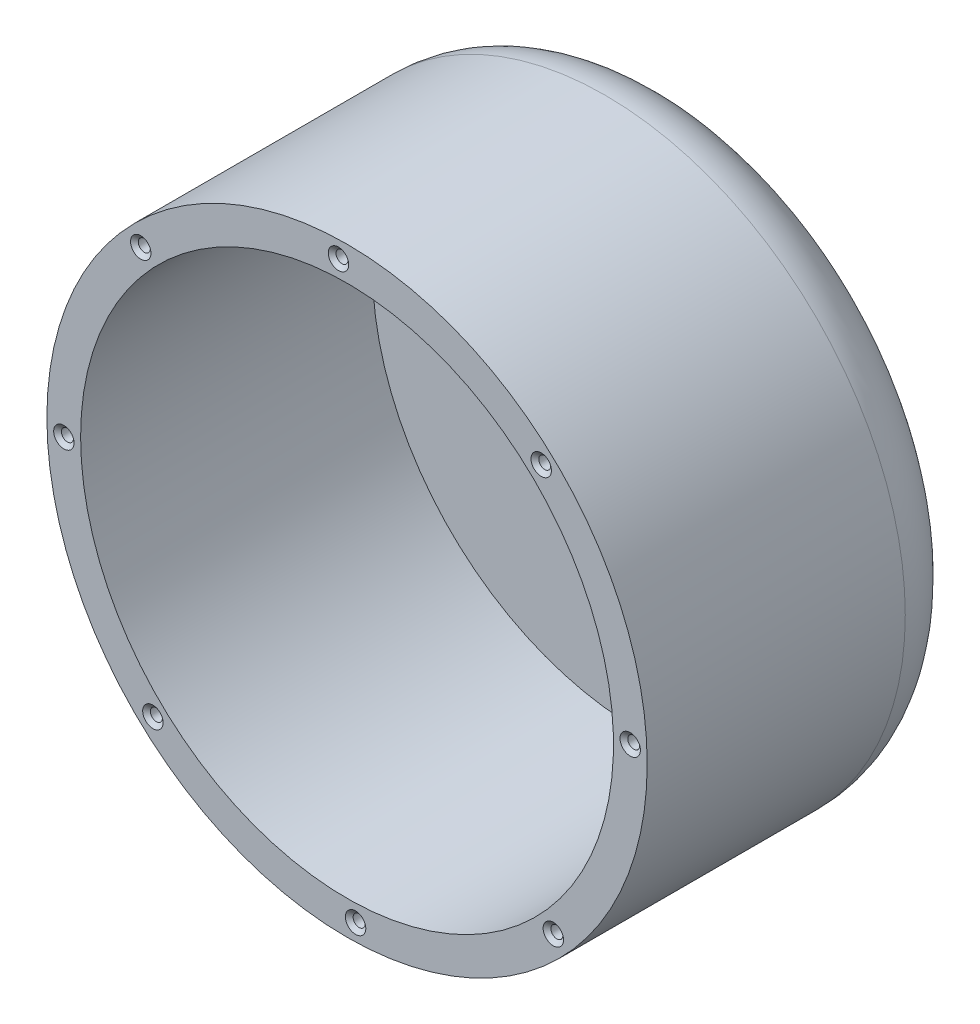
SolidWorks part; units mm, degrees
ref_plane "Front Plane" through (0, 0, 0) normal (0, 0, 1) x (1, 0, 0)
ref_plane "Top Plane" through (0, 0, 0) normal (0, 1, 0) x (1, 0, 0)
ref_plane "Right Plane" through (0, 0, 0) normal (1, 0, 0) x (0, 0, -1)
sketch "Sketch1" plane through (0, 0, 0) normal (0, 0, 1) x (1, 0, 0)
  circle A0 centre (0, 0) radius 44.5
  dimension "D1" = 89
extrude "Boss-Extrude1" add sketch "Sketch1" along normal mid plane 48.26
shell "Shell1" thickness 5 removed face at (44.5, 0, 24.13)
hole_wizard "CSK for #0 Flat Head Machine Screw (100)1" positions "3DSketch1" profile "Sketch5" countersink size "#0" standard "ANSI Inch"
sketch3d "3DSketch1"
  circle A0 centre (0, 0, 24.13) radius 39.5 construction
  point P0 (-1.2693, 41.9808, 24.13)
  point P7 (0, 0, 63.63)
  point P8 (65.1395, 21.7841, 0)
  dimension "D1" = 42
sketch "Sketch5" plane through (-1.2693, 41.9808, 24.13) normal (1, 0, 0) x (0, -1, 0)
  line L0 (0, 0) -> (0, 3.0742)
  line L1 (0, 3.0742) -> (0.889, 2.54)
  line L2 (0.889, 2.54) -> (0.889, 0.5222)
  line L3 (0.889, 0.5222) -> (1.5113, 0)
  line L5 (1.5113, 0) -> (0, 0)
  line L6 (-0.889, 0.5222) -> (-1.5113, 0) construction
  line L10 (0, 3.0742) -> (-0.889, 2.54) construction
  line L11 (0, -6.35) -> (0, 107.95) construction
  dimension "Hole Dia." = 1.778
  dimension "Hole Depth" = 2.54
  dimension "Near C'Sink Dia." = 3.0226
  dimension "Near C'Sink Angle" = 100
  dimension "Drill Angle" = 118
pattern_circular "CirPattern1" count 8 over 360 about axis through (0, 0, 24.13) along (0, 0, -1) of "CSK for #0 Flat Head Machine Screw (100)1"
fillet "Fillet1" radius 10 1 edges at (44.5, 0, -24.13)
scale "Scale1" scale about centroid uniform scaling yes scale factor 0.5
